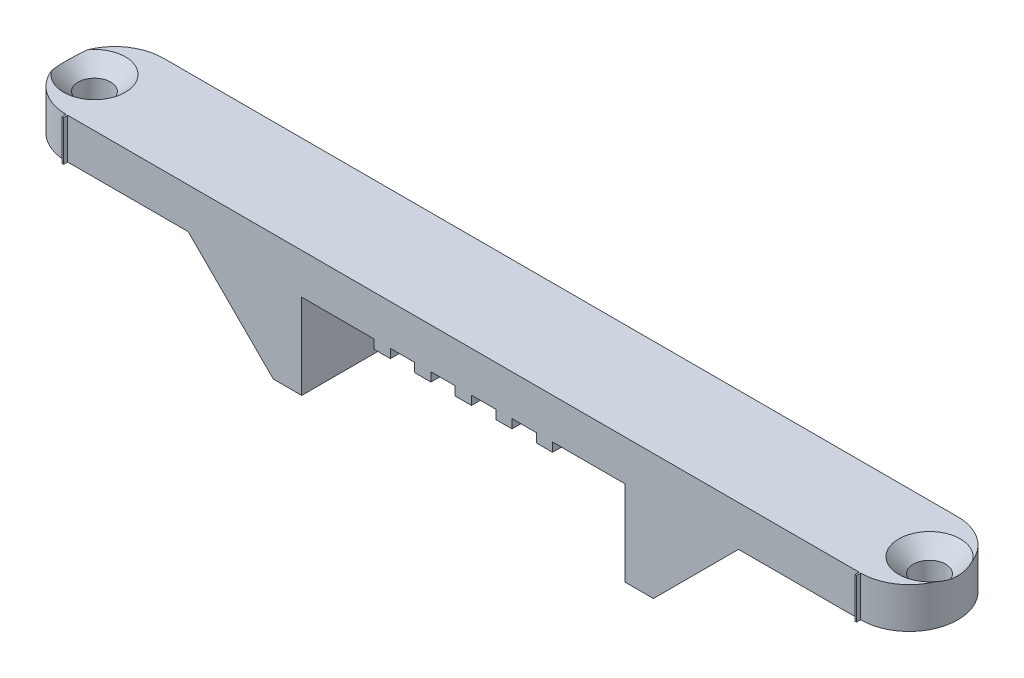
SolidWorks part; units mm, degrees
ref_plane "Front Plane" through (0, 0, 0) normal (0, 0, 1) x (1, 0, 0)
ref_plane "Top Plane" through (0, 0, 0) normal (0, 1, 0) x (1, 0, 0)
ref_plane "Right Plane" through (0, 0, 0) normal (1, 0, 0) x (0, 0, -1)
sketch "Sketch1" plane through (0, 0, 0) normal (0, 1, 0) x (1, 0, 0)
  line L0 (-49, 0) -> (49, 0) construction
  line L1 (-49, 6) -> (49, 6)
  line L2 (-49, -6) -> (49, -6)
  arc A0 (-49, 6) -> (-49, -6) centre (-49, 0) ccw
  arc A1 (49, -6) -> (49, 6) centre (49, 0) ccw
  circle A2 centre (-51.5, 0) radius 1.5
  circle A3 centre (51.5, 0) radius 1.5
  point P2 (0, 0)
  point P12 (-55, 0)
  point P13 (55, 0)
  dimension "D3" = 3
  dimension "D4" = 3.5
  dimension "D1" = 110
  dimension "D2" = 12
  dimension "D5" = 3.5
extrude "Boss-Extrude1" add sketch "Sketch1" along normal blind 3 contours L2 A1 L1 A0 | A2 | A3
sketch "Sketch4" plane through (0, 0, 0) normal (0, -1, 0) x (1, 0, 0)
  line L0 (-19.94, 6) -> (-19.94, -6)
  line L1 (-49, 6) -> (49, 6) construction
  line L2 (-49, -6) -> (49, -6) construction
  line L3 (-19.94, -6) -> (-23.44, -6)
  line L4 (-23.44, -6) -> (-23.44, 6)
  line L5 (-23.44, 6) -> (-19.94, 6)
  line L6 (0, 6) -> (0, -6) construction
  line L7 (-19.94, 5.075) -> (-19.94, -14.3256) construction
  line L8 (23.44, -6) -> (23.44, 6)
  line L9 (19.94, -6) -> (23.44, -6)
  line L10 (19.94, 6) -> (19.94, -6)
  line L11 (23.44, 6) -> (19.94, 6)
  dimension "D1" = 0
  dimension "D2" = 3.5
extrude "Boss-Extrude3" add sketch "Sketch4" along normal blind 10.5
sketch "Sketch5" plane through (0, 0, 0) normal (0, -1, 0) x (1, 0, 0)
  line L1 (4, 6) -> (4, -6)
  line L2 (4, 6) -> (6, 6)
  line L6 (-19.94, -6) -> (19.94, -6) construction
  line L7 (-1, 6) -> (1, 6)
  line L8 (-1, 6) -> (-1, -6)
  line L9 (-1, -6) -> (1, -6)
  line L10 (1, 6) -> (1, -6)
  line L11 (-1, 6) -> (1, -6) construction
  line L12 (-1, -6) -> (1, 6) construction
  line L13 (6, 6) -> (6, -6)
  line L14 (4, -6) -> (6, -6)
  line L15 (9, 6) -> (9, -6)
  line L16 (9, 6) -> (11, 6)
  line L17 (11, 6) -> (11, -6)
  line L18 (9, -6) -> (11, -6)
  line L19 (-4, 6) -> (-4, -6)
  line L20 (-6, -6) -> (-4, -6)
  line L21 (-6, 6) -> (-6, -6)
  line L22 (-6, 6) -> (-4, 6)
  line L23 (-9, 6) -> (-9, -6)
  line L24 (-11, -6) -> (-9, -6)
  line L25 (-11, 6) -> (-11, -6)
  line L26 (-11, 6) -> (-9, 6)
  point P0 (0, 0)
  dimension "D1" = 2
  dimension "D2" = 3
  dimension "D3" = 3
extrude "Boss-Extrude4" add sketch "Sketch5" along normal blind 1.1
sketch "Sketch6" plane through (0, 0, 6) normal (0, 0, 1) x (1, 0, 0)
  line L0 (49, 0) -> (49, 3)
  line L1 (49, 3) -> (48.8, 3)
  line L2 (-49, 3) -> (49, 3) construction
  line L3 (48.8, 3) -> (48.8, 0)
  line L4 (23.44, 0) -> (49, 0) construction
  line L5 (48.8, 0) -> (49, 0)
  line L6 (0, 0) -> (0, 3) construction
  line L7 (-48.8, 0) -> (-49, 0)
  line L8 (-48.8, 3) -> (-48.8, 0)
  line L9 (-49, 3) -> (-48.8, 3)
  line L10 (-49, 0) -> (-49, 3)
  dimension "D1" = 0.2
extrude "Boss-Extrude5" add sketch "Sketch6" along normal blind 0.5 contours L0 L1 L3 L5 | L8 L7 L10 L9
chamfer "Chamfer1" distance 10.5 6 edges at (-23.44, 0, 0) (-23.44, -5.25, 6) (-23.44, -5.25, -6) (23.44, 0, 0) (23.44, -5.25, -6) (23.44, -5.25, 6)
sketch "Sketch10" plane through (0, 3, 0) normal (0, 1, 0) x (1, 0, 0)
  line L8 (-49, -6) -> (-49, -6.5)
  line L9 (-49, -6.5) -> (-48.8, -6.5)
  line L10 (-48.8, -6.5) -> (-48.8, -6)
  line L11 (-48.8, -6) -> (48.8, -6)
  line L12 (48.8, -6) -> (48.8, -6.5)
  line L13 (48.8, -6.5) -> (49, -6.5)
  line L14 (49, -6.5) -> (49, -6)
  line L15 (49, 6) -> (-49, 6)
  line L16 (-49, -6) -> (-49, -6.5)
  line L17 (-49, -6.5) -> (-48.8, -6.5)
  line L18 (-48.8, -6.5) -> (-48.8, -6)
  line L19 (-48.8, -6) -> (48.8, -6)
  line L20 (48.8, -6) -> (48.8, -6.5)
  line L21 (48.8, -6.5) -> (49, -6.5)
  line L22 (49, -6.5) -> (49, -6)
  line L23 (49, 6) -> (-49, 6)
  circle A0 centre (-51.5, 0) radius 1.5 construction
  circle A1 centre (-51.5, 0) radius 1.5
  arc A2 (-49, 6) -> (-49, -6) centre (-49, 0) ccw
  arc A3 (49, -6) -> (49, 6) centre (49, 0) ccw
  arc A4 (-49, 6) -> (-49, -6) centre (-49, 0) ccw
  arc A5 (49, -6) -> (49, 6) centre (49, 0) ccw
  circle A6 centre (51.5, 0) radius 1.5 construction
  circle A7 centre (51.5, 0) radius 1.5
  dimension "D1" = 0
extrude "Boss-Extrude6" add sketch "Sketch10" along normal blind 2 contours A4 L16 L17 L18 L19 L20 L21 L22 A5 L23
hole_wizard "CSK for M4 SFHCS1" positions "Sketch11" profile "Sketch12" countersink size "M4" standard "ANSI Metric"
sketch "Sketch11" plane through (0, 5, 0) normal (0, 1, 0) x (1, 0, 0)
  point P0 (51.5, 0)
  point P3 (-51.5, 0)
sketch "Sketch12" plane through (51.5, 5, 0) normal (1, 0, 0) x (0, 0, 1)
  line L0 (0, 0) -> (0, 32)
  line L1 (0, 32) -> (2, 30.7983)
  line L2 (2, 30.7983) -> (2, 1.8)
  line L3 (2, 1.8) -> (3.8, 0)
  line L5 (3.8, 0) -> (0, 0)
  line L6 (-2, 1.8) -> (-3.8, 0) construction
  line L10 (0, 32) -> (-2, 30.7983) construction
  line L11 (0, -6.35) -> (0, 107.95) construction
  dimension "Hole Dia." = 4
  dimension "Hole Depth" = 32
  dimension "Near C'Sink Dia." = 7.6
  dimension "Near C'Sink Angle" = 90
  dimension "Drill Angle" = 118
